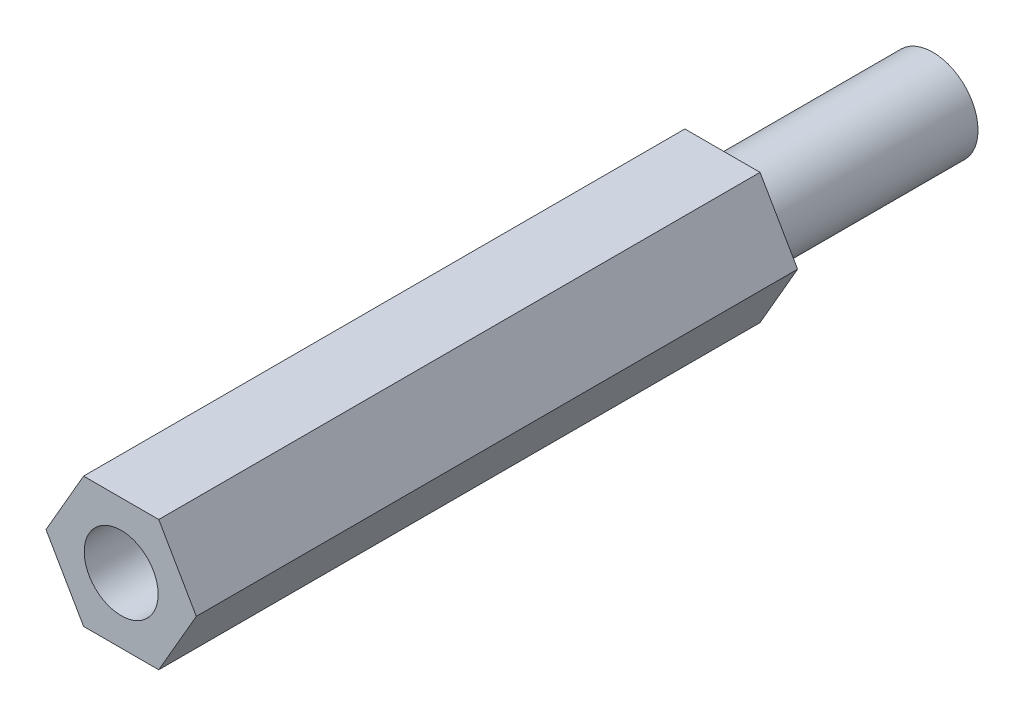
SolidWorks part; units mm, degrees
material "201 ricotto (SS)"
ref_plane "Piano frontale" through (0, 0, 0) normal (0, 0, 1) x (1, 0, 0)
ref_plane "Piano superiore" through (0, 0, 0) normal (0, 1, 0) x (1, 0, 0)
ref_plane "Piano destro" through (0, 0, 0) normal (1, 0, 0) x (0, 0, -1)
sketch "Schizzo1" plane through (0, 0, 0) normal (0, 0, 1) x (1, 0, 0)
  line L0 (1.25, -2.1651) -> (2.5, 0)
  line L1 (2.5, 0) -> (1.25, 2.1651)
  line L2 (1.25, 2.1651) -> (-1.25, 2.1651)
  line L3 (-1.25, 2.1651) -> (-2.5, 0)
  line L4 (-2.5, 0) -> (-1.25, -2.1651)
  line L5 (-1.25, -2.1651) -> (1.25, -2.1651)
extrude "Estrusione-Estrusione1" add sketch "Schizzo1" against normal blind 20
sketch "Schizzo2" plane through (0, 0, -20) normal (0, 0, -1) x (-1, 0, 0)
  circle A0 centre (0, 0) radius 1.5
extrude "Estrusione-Estrusione2" add sketch "Schizzo2" along normal blind 7
hole_wizard "Foro1" positions "Schizzo4" profile "Schizzo3" legacy
sketch "Schizzo4" plane through (0, 0, 0) normal (0, 0, 1) x (1, 0, 0)
  point P0 (0, 0)
sketch "Schizzo3" plane through (0, 0, 0) normal (1, 0, 0) x (0, -1, 0)
  line L0 (0, 0) -> (0, 7)
  line L1 (0, 7) -> (1.2295, 7)
  line L2 (1.2295, 7) -> (1.2295, 0)
  line L3 (1.2295, 0) -> (0, 0)
  line L4 (0, 110) -> (0, -10) construction
  dimension "Diameter" = 2.459
  dimension "Depth" = 7
equation "\"Altezza\"= 20mm"
equation "\"D1@Estrusione-Estrusione1\"=\"Altezza\""
